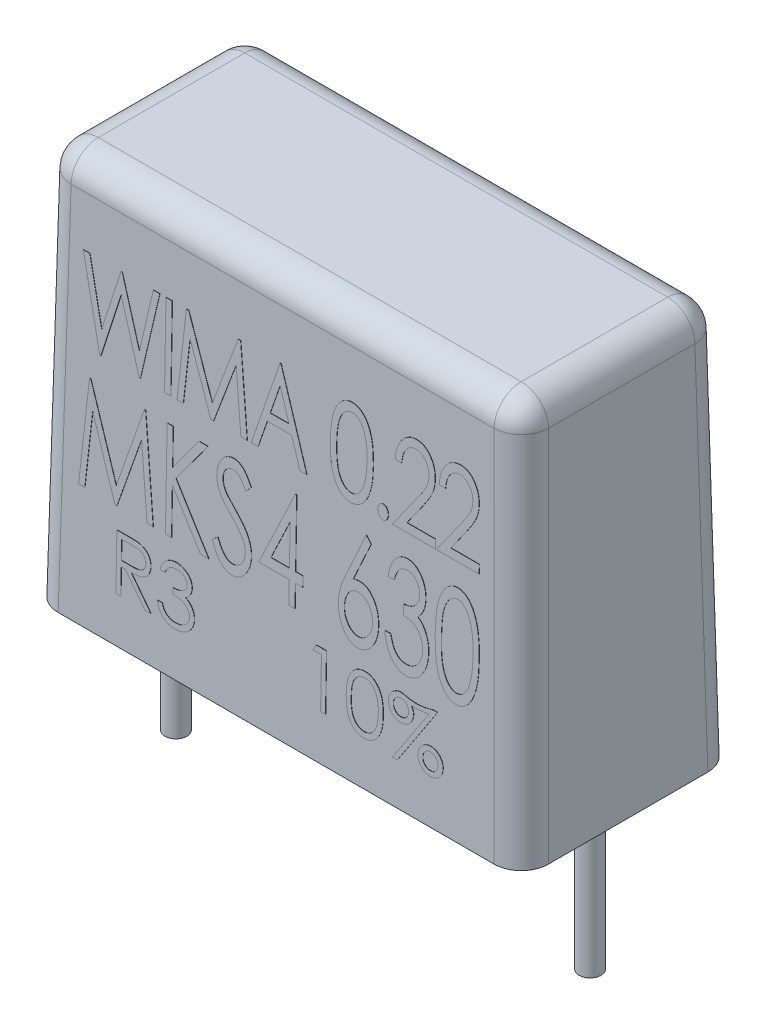
SolidWorks part; units mm, degrees
ref_plane "Front Plane" through (0, 0, 0) normal (0, 0, 1) x (1, 0, 0)
ref_plane "Top Plane" through (0, 0, 0) normal (0, 1, 0) x (1, 0, 0)
ref_plane "Right Plane" through (0, 0, 0) normal (1, 0, 0) x (0, 0, -1)
sketch "Sketch1" plane through (0, 0, 0) normal (0, 1, 0) x (1, 0, 0)
  line L1 (-9, 3.925) -> (9, 3.925)
  line L2 (-9, 3.925) -> (-9, -3.925)
  line L3 (-9, -3.925) -> (9, -3.925)
  line L4 (9, 3.925) -> (9, -3.925)
  line L5 (-9, 3.925) -> (9, -3.925) construction
  line L6 (-9, -3.925) -> (9, 3.925) construction
  point P0 (0, 0)
  dimension "D1" = 7.85
  dimension "D2" = 18
extrude "Boss-Extrude1" add sketch "Sketch1" along normal blind 14.6 draft 1
fillet "Fillet1" radius 1 8 edges at (0, 14.6, 3.6702) (-8.7452, 14.6, 0) (0, 14.6, -3.6702) (8.7452, 14.6, 0) (-8.8726, 7.3, 3.7976) (-8.8726, 7.3, -3.7976) (8.8726, 7.3, -3.7976) (8.8726, 7.3, 3.7976)
sketch "Sketch2" plane through (0, 0, 0) normal (0, -1, 0) x (1, 0, 0)
  line L0 (0, 1.8912) -> (0, -1.1442) construction
  line L1 (8, 0) -> (8, -0.7473) construction
  line L2 (9, 2.9252) -> (9, -2.9252) construction
  circle A0 centre (7.6, 0) radius 0.4
  circle A1 centre (-7.6, 0) radius 0.4
  dimension "D1" = 0.8
  dimension "D2" = 1
extrude "Boss-Extrude2" add sketch "Sketch2" along normal blind 5.5
sketch "Sketch3" plane through (0, 0, 0) normal (0, 0, 1) x (1, 0, 0)
  line L0 (-7.8465, 8.8) -> (7.8465, 8.8) construction
  line L1 (-7.7625, 13.6175) -> (-8.0002, 0) construction
  line L2 (8.0002, 0) -> (7.7625, 13.6175) construction
  line L3 (-7.9234, 4.4) -> (7.9234, 4.4) construction
  line L4 (-8.0002, 0) -> (8.0002, 0) construction
  line L5 (-7.9714, 1.65) -> (7.9714, 1.65) construction
  text T0 "WIMA 0.22" font "Century Gothic" height 3
  text T1 "MKS4 630" font "Century Gothic" height 3.5
  text T2 "R3     10%" font "Century Gothic" height 2
  point P11 (7.9869, 0.7606)
  point P14 (-7.9861, 0.8065)
  dimension "D1" = 4.4
  dimension "D2" = 4.4
  dimension "D3" = 1.65
extrude "Boss-Extrude3" add sketch "Sketch3" along normal offset from surface (3.7814 mm away) 0.01
